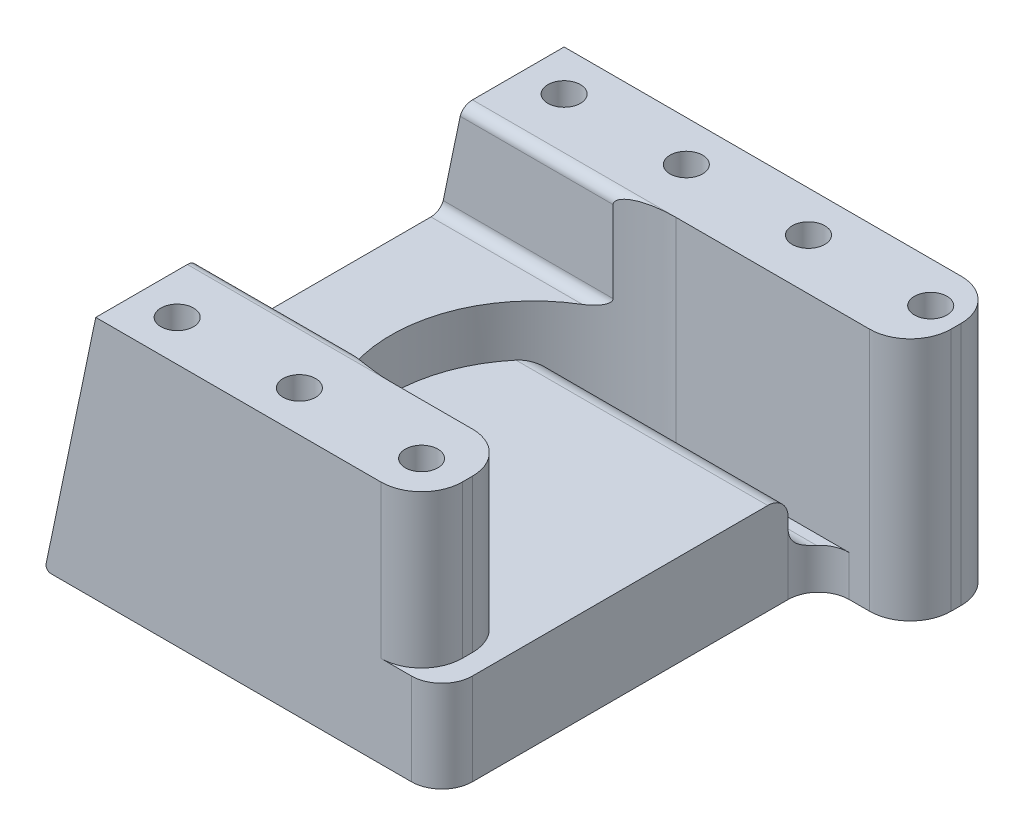
SolidWorks part; units mm, degrees
material "PEI"
ref_plane "Front Plane" through (0, 0, 0) normal (0, 0, 1) x (1, 0, 0)
ref_plane "Top Plane" through (0, 0, 0) normal (0, 1, 0) x (1, 0, 0)
ref_plane "Right Plane" through (0, 0, 0) normal (1, 0, 0) x (0, 0, -1)
sketch "Sketch2" plane through (0, 0, 0) normal (0, 1, 0) x (1, 0, 0)
  line L0 (0, 0) -> (0, 19)
  line L1 (0, 0) -> (-12, 0)
  line L2 (-12, 0) -> (-12, 19)
  line L3 (0, 0) -> (4, 0)
  line L4 (16, -23) -> (-16, -23)
  line L5 (16, -23) -> (16, 23)
  line L6 (16, 23) -> (-16, 23)
  line L7 (-16, -23) -> (-16, 23)
  line L8 (16, -23) -> (-16, 23) construction
  line L9 (16, 23) -> (-16, -23) construction
  line L10 (4, 14) -> (16, 14)
  line L11 (4, -14) -> (16, -14)
  line L12 (12, 19) -> (24.0037, 19)
  line L13 (16, 14) -> (27, 14)
  line L14 (16, 14) -> (16, 23)
  line L15 (16, 23) -> (27, 23)
  line L16 (27, 14) -> (27, 23)
  circle A0 centre (-12, 19) radius 1.6
  circle A1 centre (0, 19) radius 1.6
  circle A2 centre (12, 19) radius 1.6
  circle A4 centre (0, -19) radius 1.6
  circle A5 centre (-12, -19) radius 1.6
  circle A6 centre (4, 0) radius 14
  circle A7 centre (12, -19) radius 1.6
  circle A8 centre (24.0037, 19) radius 1.6
  dimension "D3" = 3.2
  dimension "D4" = 3.2
  dimension "D7" = 28
  dimension "D12" = 3.2
  dimension "D1" = 12
  dimension "D2" = 19
  dimension "D5" = 19
  dimension "D6" = 4
  dimension "D8" = 46
  dimension "D9" = 32
  dimension "D10" = 15
  dimension "D11" = 12.0037
extrude "Boss-Extrude1" add sketch "Sketch2" along normal blind 24 contours A6 L5 L6 L7 L4 A0 A1 A4 A2 A5 | A8 L5 L13 L16 L15 region at (-7.6743, 0, -8.7015) region at (21.2786, 0, -18.4558)
sketch "Sketch4" plane through (0, 0, 23) normal (0, 0, 1) x (1, 0, 0)
  line L0 (-16, 0) -> (-21, 0)
  line L1 (-21, 0) -> (-16, 24)
  line L4 (-16, 0) -> (16, 0)
  line L5 (16, 0) -> (16, 24)
  line L6 (16, 24) -> (-16, 24)
  line L7 (-16, 24) -> (-16, 0)
  line L8 (-16, 0) -> (16, 0)
  line L10 (16, 24) -> (-16, 24)
  line L11 (-16, 24) -> (-16, 0)
  line L14 (16, 0) -> (16, 24)
  line M9 (-16, 24) -> (-16, 0)
  dimension "D2" = 5
  dimension "D1" = 0
extrude "Boss-Extrude2" add sketch "Sketch4" against normal up to surface (46 mm away) contours L1 L0 M9 region at (-17.6667, 8, 23) up to face at (5.5, 12, -23)
sketch "Sketch5" plane through (0, 24, 0) normal (0, 1, 0) x (1, 0, 0)
  line L0 (0, 0) -> (-21, 0)
  line L1 (0, 13) -> (-21, 13)
  line L2 (0, -13) -> (-21, -13)
  line L4 (-16, -23) -> (-16, 23)
  line L5 (-16, 23) -> (-21, 23)
  line L6 (-21, 23) -> (-21, -23)
  line L7 (-21, -23) -> (-16, -23)
  line L8 (-16, -23) -> (-16, 23)
  line L9 (-16, 23) -> (-21, 23)
  line L10 (-21, 23) -> (-21, -23)
  line L11 (-21, -23) -> (-16, -23)
  line L15 (4, 14) -> (27, 14)
  line L16 (16, -23) -> (16, -14)
  line L17 (27, 23) -> (-16, 23)
  line L18 (-16, 23) -> (-16, -23)
  line L19 (-16, -23) -> (16, -23)
  line L20 (27, 14) -> (27, 23)
  line L21 (27, 14) -> (27, 23)
  line L22 (4, 14) -> (27, 14)
  line L23 (16, -23) -> (16, -14)
  line L24 (27, 23) -> (-16, 23)
  line L25 (-16, 23) -> (-16, -23)
  line L26 (-16, -23) -> (16, -23)
  line L30 (16, -14) -> (4, -14)
  line L31 (16, -14) -> (4, -14)
  arc A1 (4, 14) -> (4, -14) centre (4, 0) ccw
  arc A2 (4, 14) -> (4, -14) centre (4, 0) ccw
  arc M16 (4, -14) -> (4, 14) centre (4, 0) cw
  line M20 (-16, 23) -> (-16, -23)
  dimension "D1" = 0
  dimension "D2" = 0
  dimension "D3" = 13
  dimension "D4" = 13
extrude "Cut-Extrude1" cut sketch "Sketch5" against normal blind 10 contours L1 L0 M16 M20 | L1 L10 L0 M20 | L2 L0 M16 M20 | L0 L10 L2 M20 region at (-11.4463, 24, 7.5042) region at (-11.4463, 24, -7.5042) region at (-18.5, 24, 6.5) region at (-18.5, 24, -6.5)
fillet "Fillet1" radius 1 4 edges at (-9.6397, 14, 13) (-9.6397, 14, -13) (-8.5981, 24, 13) (-8.5981, 24, -13)
fillet "Fillet2" radius 0.5 1 edges at (-21, 0, 0)
fillet "Fillet3" radius 4 4 edges at (16, 12, 14) (16, 12, 23) (27, 12, -23) (27, 12, -14)
sketch "Sketch6" plane through (0, 0, 0) normal (0, -1, 0) x (1, 0, 0)
  line L0 (18, 0) -> (18, -14)
  line L1 (18, 0) -> (18, 14)
  line L2 (12, 14) -> (18, 14)
  line L3 (12, 23) -> (18, 23)
  line L4 (18, 23) -> (18, 14)
  line L6 (4, 14) -> (12, 14)
  line L7 (12, 23) -> (-20.3851, 23)
  line L8 (-20.3851, 23) -> (-20.3851, -23)
  line L9 (-20.3851, -23) -> (23, -23)
  line L11 (23, -14) -> (4, -14)
  line L12 (4, 14) -> (12, 14)
  line L13 (12, 23) -> (-20.3851, 23)
  line L14 (-20.3851, 23) -> (-20.3851, -23)
  line L15 (-20.3851, -23) -> (23, -23)
  line L17 (23, -14) -> (4, -14)
  line L23 (27, -19) -> (27, -18)
  line L24 (27, -19) -> (27, -18)
  line L25 (16, 18) -> (16, 19)
  line L26 (16, 18) -> (16, 19)
  circle A0 centre (4, 0) radius 14
  arc A3 (12, 14) -> (16, 18) centre (12, 18) ccw
  arc A4 (16, 19) -> (12, 23) centre (12, 19) ccw
  arc A5 (4, 14) -> (4, -14) centre (4, 0) ccw
  arc A6 (12, 14) -> (16, 18) centre (12, 18) ccw
  arc A7 (16, 19) -> (12, 23) centre (12, 19) ccw
  arc A8 (4, 14) -> (4, -14) centre (4, 0) ccw
  arc A12 (23, -23) -> (27, -19) centre (23, -19) ccw
  arc A13 (23, -23) -> (27, -19) centre (23, -19) ccw
  arc A14 (27, -18) -> (23, -14) centre (23, -18) ccw
  arc A15 (27, -18) -> (23, -14) centre (23, -18) ccw
  line M10 (4, 14) -> (12, 14)
  arc M11 (12, 14) -> (16, 18) centre (12, 18) ccw
  arc M12 (16, 19) -> (12, 23) centre (12, 19) ccw
  line M17 (23, -14) -> (4, -14)
  arc M18 (4, -14) -> (4, 14) centre (4, 0) cw
  dimension "D1" = 0
extrude "Boss-Extrude3" add sketch "Sketch6" against normal blind 9 contours A0 L0 M17 | A0 M18 | L4 L3 L2 M12 M11 | A0 L1 L2 M10 region at (14.8728, 0, 10.8728) region at (4, 0, 0) region at (14.8728, 0, -10.8728) region at (16.4771, 0, 18.5)
fillet "Fillet4" radius 3 2 edges at (18, 4.5, 23) (18, 4.5, -14)
sketch "Sketch7" plane through (0, 9, 0) normal (0, 1, 0) x (1, 0, 0)
  line L0 (18, 11) -> (-4.6603, 11)
  line L5 (12, -23) -> (15, -23)
  line L6 (18, -20) -> (18, 11)
  line L7 (21, 14) -> (4, 14)
  line L8 (4, -14) -> (12, -14)
  line L9 (16, -18) -> (16, -19)
  line L10 (12, -23) -> (15, -23)
  line L11 (18, -20) -> (18, 11)
  line L12 (21, 14) -> (4, 14)
  line L13 (4, -14) -> (12, -14)
  line L14 (16, -18) -> (16, -19)
  arc A5 (15, -23) -> (18, -20) centre (15, -20) ccw
  arc A6 (21, 14) -> (18, 11) centre (21, 11) ccw
  arc A7 (4, 14) -> (4, -14) centre (4, 0) ccw
  arc A8 (16, -18) -> (12, -14) centre (12, -18) ccw
  arc A9 (12, -23) -> (16, -19) centre (12, -19) ccw
  arc A10 (15, -23) -> (18, -20) centre (15, -20) ccw
  arc A11 (21, 14) -> (18, 11) centre (21, 11) ccw
  arc A12 (4, 14) -> (4, -14) centre (4, 0) ccw
  arc A13 (16, -18) -> (12, -14) centre (12, -18) ccw
  arc A14 (12, -23) -> (16, -19) centre (12, -19) ccw
  arc M14 (18, 11) -> (21, 14) centre (21, 11) cw
  line M15 (21, 14) -> (4, 14)
  arc M16 (4, 14) -> (4, -14) centre (4, 0) ccw
  dimension "D1" = 0
extrude "Cut-Extrude2" cut sketch "Sketch7" against normal blind 5 contours L0 M14 M15 M16 region at (8.2788, 9, -12.4431)
fillet "Fillet5" radius 2 2 edges at (6.6699, 4, -11) (6.6699, 9, -11)
